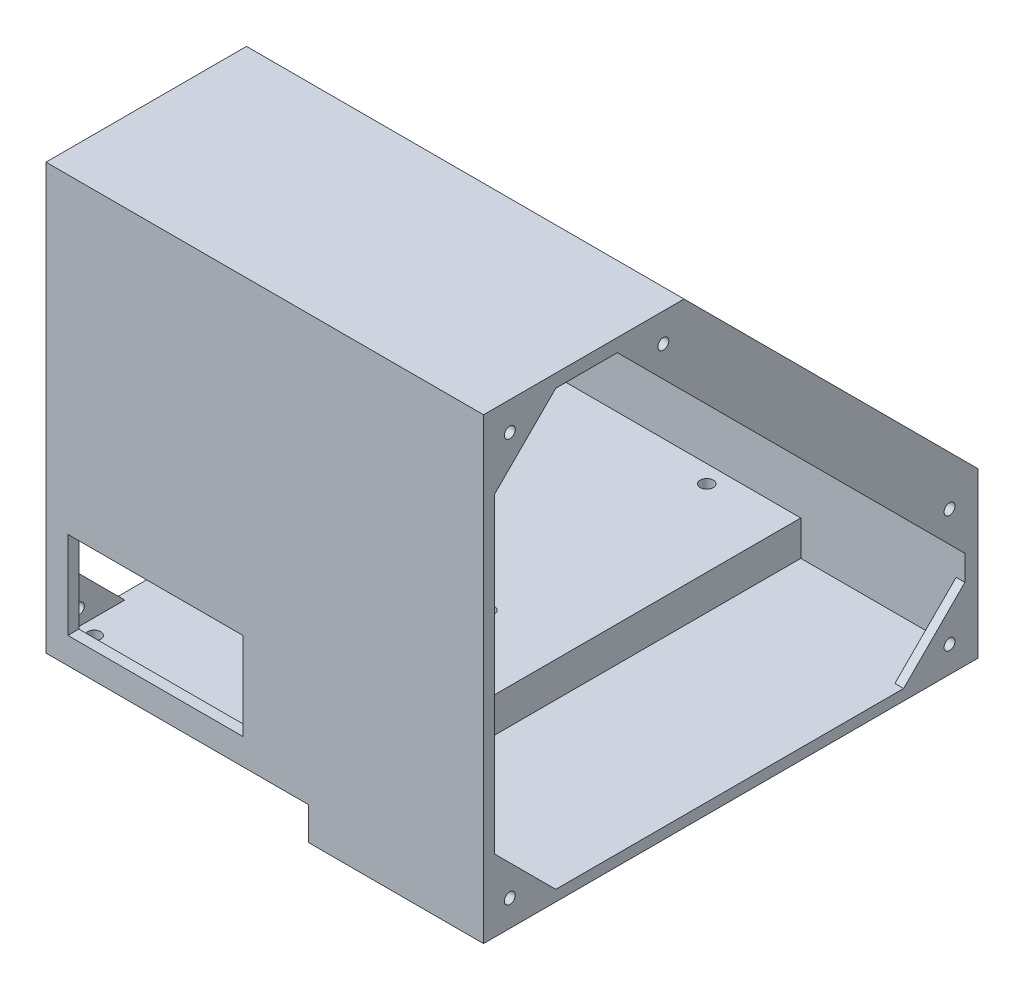
SolidWorks part; units mm, degrees
ref_plane "Front Plane" through (0, 0, 0) normal (0, 0, 1) x (1, 0, 0)
ref_plane "Top Plane" through (0, 0, 0) normal (0, 1, 0) x (1, 0, 0)
ref_plane "Right Plane" through (0, 0, 0) normal (1, 0, 0) x (0, 0, -1)
sketch "Sketch1" plane through (0, 0, 0) normal (1, 0, 0) x (0, 0, -1)
  line L0 (0, 0) -> (0, 30)
  line L1 (0, 30) -> (-67.1751, 97.1751)
  line L2 (-67.1751, 97.1751) -> (-113, 97.1751)
  line L3 (-113, 97.1751) -> (-113, 94.1751)
  line L4 (-113, 94.1751) -> (-68.4178, 94.1751)
  line L5 (-68.4178, 94.1751) -> (-3, 28.7574)
  line L6 (-3, 28.7574) -> (-3, 0)
  line L7 (-3, 0) -> (0, 0)
  line L8 (-3, 28.7574) -> (0, 28.7574) construction
  line L9 (-3, 28.7574) -> (-0.8787, 30.8787) construction
  line L10 (-68.4178, 94.1751) -> (-68.4178, 97.1751) construction
  dimension "D1" = 95
  dimension "D2" = 135
  dimension "D3" = 3
  dimension "D4" = 30
  dimension "D5" = 110
extrude "Boss-Extrude1" add sketch "Sketch1" along normal blind 100
sketch "Sketch2" plane through (0, 0, 0) normal (0, -1, 0) x (1, 0, 0)
  line L0 (100, 0) -> (0, 0) construction
  line L1 (100, 3) -> (60, 3)
  line L2 (100, 3) -> (100, 0)
  line L3 (100, 0) -> (60, 0)
  line L4 (60, 3) -> (60, 0)
  dimension "D1" = 40
extrude "Boss-Extrude2" add sketch "Sketch2" along normal blind 7.5
sketch "Sketch3" plane through (0, 0, 0) normal (0, -1, 0) x (1, 0, 0)
  line L0 (0, 3) -> (0, 113)
  line L1 (0, 113) -> (60, 113)
  line L2 (60, 113) -> (60, 3)
  line L3 (60, 3) -> (0, 3)
  line L4 (100, 3) -> (0, 3) construction
  line L5 (60, 3) -> (0, 3) construction
  dimension "D1" = 110
extrude "Boss-Extrude3" add sketch "Sketch3" against normal blind 3
sketch "Sketch4" plane through (0, 0, 3) normal (0, 0, 1) x (1, 0, 0)
  line L0 (60, 3) -> (60, -7.5)
  line L1 (60, -7.5) -> (100, -7.5)
  line L2 (100, -7.5) -> (100, -5)
  line L3 (100, 28.7574) -> (100, -7.5) construction
  line L4 (100, -5) -> (62.5, -5)
  line L5 (62.5, -5) -> (62.5, 3)
  line L6 (62.5, 3) -> (60, 3)
  dimension "D1" = 2.5
extrude "Boss-Extrude4" add sketch "Sketch4" along normal up to surface (110 mm away) up to face at (30, 1.5, 113)
sketch "Sketch5" plane through (0, 94.1751, 0) normal (0, -1, 0) x (1, 0, 0)
  line L0 (100, 113) -> (100, 68.4178) construction
  line L1 (0, 113) -> (100, 113)
  line L2 (0, 113) -> (0, 110.5)
  line L3 (0, 110.5) -> (100, 110.5)
  line L4 (100, 113) -> (100, 110.5)
  dimension "D1" = 2.5
extrude "Boss-Extrude5" add sketch "Sketch5" along normal up to next
sketch "Sketch6" plane through (0, 0, 0) normal (0, -1, 0) x (1, 0, 0)
  circle A0 centre (5, 107) radius 1.5 construction
  circle A1 centre (45, 107) radius 1.5 construction
  circle A2 centre (45, 57) radius 1.5 construction
  circle A3 centre (5, 57) radius 1.5 construction
  circle A4 centre (5, 7) radius 1.5 construction
  circle A5 centre (45, 7) radius 1.5 construction
  circle A6 centre (5, 107) radius 1.5
  circle A7 centre (45, 107) radius 1.5
  circle A8 centre (45, 57) radius 1.5
  circle A9 centre (5, 57) radius 1.5
  circle A10 centre (5, 7) radius 1.5
  circle A11 centre (45, 7) radius 1.5
extrude "Cut-Extrude1" cut sketch "Sketch6" against normal up to next
sketch "Sketch7" plane through (100, 0, 0) normal (1, 0, 0) x (0, 0, -1)
  line L0 (-110.5, -5) -> (-110.5, 9)
  line L1 (-110.5, -5) -> (-110.5, 94.1751) construction
  line L2 (-110.5, 9) -> (-96.5, -5)
  line L3 (-110.5, -5) -> (-3, -5) construction
  line L4 (-96.5, -5) -> (-110.5, -5)
  line L5 (-110.5, 94.1751) -> (-110.5, 80.1751)
  line L6 (-110.5, 80.1751) -> (-96.5, 94.1751)
  line L7 (-110.5, 94.1751) -> (-68.4178, 94.1751) construction
  line L8 (-96.5, 94.1751) -> (-110.5, 94.1751)
  line L9 (-82.4178, 94.1751) -> (-3, 14.7574)
  line L10 (-3, 28.7574) -> (-3, -5) construction
  line L11 (-3, 14.7574) -> (-3, 28.7574)
  line L12 (-3, 28.7574) -> (-68.4178, 94.1751)
  line L13 (-68.4178, 94.1751) -> (-82.4178, 94.1751)
  line L14 (-17, -5) -> (-3, 9)
  line L15 (-3, 9) -> (-3, -5)
  line L16 (-3, -5) -> (-17, -5)
  line L17 (-110.5, -5) -> (-103.5, 2) construction
  line L18 (-3, -5) -> (-10, 2) construction
  line L19 (-3, 28.7574) -> (-10, 21.7574) construction
  line L20 (-68.4178, 94.1751) -> (-75.4178, 87.1751) construction
  line L21 (-110.5, 94.1751) -> (-103.5, 87.1751) construction
  circle A0 centre (-107, -1.5) radius 1.25
  circle A1 centre (-6.5, -1.5) radius 1 construction
  circle A2 centre (-6.5, -1.5) radius 1.25
  circle A3 centre (-6.5, 25.2574) radius 1.25
  circle A4 centre (-71.9178, 90.6751) radius 1.25
  circle A5 centre (-107, 90.6751) radius 1.25
  dimension "D2" = 2
  dimension "D1" = 14
  dimension "D3" = 0.25
extrude "Boss-Extrude6" add sketch "Sketch7" against normal blind 2
sketch "Sketch8" plane through (0, 15, -15) normal (0, 0.7071, -0.7071) x (1, 0, 0)
  line L0 (96.675, -112.2132) -> (100, -112.2132) construction
  line L1 (96.675, -25.2132) -> (3.325, -25.2132) construction
  line L2 (96.675, -25.2132) -> (96.675, -112.2132) construction
  line L3 (96.675, -112.2132) -> (3.325, -112.2132) construction
  line L4 (3.325, -25.2132) -> (3.325, -112.2132) construction
  line L5 (100, -21.2132) -> (100, -116.2132) construction
  line L6 (96.675, -112.2132) -> (96.675, -116.2132) construction
  line L7 (100, -116.2132) -> (0, -116.2132) construction
  line L8 (3.325, -21.2132) -> (3.325, -25.2132) construction
  line L9 (100, -21.2132) -> (0, -21.2132) construction
  line L10 (3.325, -25.2132) -> (0, -25.2132) construction
  line L11 (0, -21.2132) -> (0, -116.2132) construction
  line L12 (96.675, -109.4882) -> (93.95, -109.4882) construction
  line L13 (93.95, -109.4882) -> (93.95, -112.2132) construction
  line L14 (93.95, -109.4882) -> (6.05, -109.4882) construction
  line L15 (6.05, -109.4882) -> (3.325, -109.4882) construction
  line L16 (93.95, -109.4882) -> (93.95, -44.5882) construction
  line L17 (93.95, -44.5882) -> (6.05, -44.5882) construction
  line L18 (6.05, -44.5882) -> (6.05, -109.4882) construction
  line L19 (89.025, -102.7132) -> (96.675, -102.7132) construction
  line L20 (89.025, -102.7132) -> (11.025, -102.7132)
  line L21 (89.025, -102.7132) -> (89.025, -58.8437)
  line L22 (89.025, -58.8437) -> (11.025, -58.8437)
  line L23 (11.025, -102.7132) -> (11.025, -58.8437)
  line L24 (89.025, -102.7132) -> (89.025, -112.2132) construction
  line L25 (51.495, -25.2132) -> (51.495, -33.7132) construction
  line L26 (51.495, -33.7132) -> (96.675, -33.7132) construction
  line L28 (33.175, -28.2132) -> (6.175, -28.2132)
  line L29 (33.175, -28.2132) -> (33.175, -40.2132)
  line L30 (33.175, -40.2132) -> (6.175, -40.2132)
  line L31 (6.175, -28.2132) -> (6.175, -40.2132)
  circle A0 centre (6.05, -109.4882) radius 1.5 construction
  circle A1 centre (6.05, -109.4882) radius 1.75
  circle A2 centre (93.95, -109.4882) radius 1.75
  circle A3 centre (93.95, -44.5882) radius 1.75
  circle A4 centre (6.05, -44.5882) radius 1.75
  circle A5 centre (51.495, -33.7132) radius 2.5
  dimension "D5" = 3
  dimension "D13" = 5
  dimension "D1" = 87
  dimension "D2" = 93.35
  dimension "D3" = 87.9
  dimension "D6" = 64.9
  dimension "D7" = 7.65
  dimension "D8" = 9.5
  dimension "D9" = 53.3695
  dimension "D10" = 85.65
  dimension "D11" = 8.5
  dimension "D12" = 45.18
  dimension "D14" = 63.5
  dimension "D15" = 90.5
  dimension "D16" = 27
  dimension "D17" = 3
  dimension "D18" = 12
  dimension "D4" = 0.25
extrude "Cut-Extrude2" cut sketch "Sketch8" against normal up to next
sketch "Sketch9" plane through (0, 12.8787, -12.8787) normal (0, -0.7071, 0.7071) x (1, 0, 0)
  line L0 (89.025, 58.8437) -> (89.025, 49.7132) construction
  line L1 (5.025, 49.7132) -> (92.025, 49.7132)
  line L2 (5.025, 49.7132) -> (5.025, 105.7132)
  line L3 (5.025, 105.7132) -> (92.025, 105.7132)
  line L4 (92.025, 49.7132) -> (92.025, 105.7132)
  line L5 (89.025, 58.8437) -> (92.025, 58.8437) construction
  line L6 (11.025, 102.7132) -> (11.025, 105.7132) construction
  line L7 (11.025, 102.7132) -> (5.025, 102.7132) construction
  line L8 (11.025, 102.7132) -> (89.025, 102.7132) construction
  line L9 (6.175, 28.2132) -> (33.175, 28.2132) construction
  line L10 (33.175, 28.2132) -> (33.175, 40.2132) construction
  line L11 (33.175, 40.2132) -> (6.175, 40.2132) construction
  line L12 (6.175, 40.2132) -> (6.175, 28.2132) construction
  line L13 (6.175, 28.2132) -> (33.175, 28.2132) construction
  line L14 (33.175, 28.2132) -> (33.175, 40.2132) construction
  line L15 (33.175, 40.2132) -> (6.175, 40.2132) construction
  line L16 (6.175, 40.2132) -> (6.175, 28.2132) construction
  line L17 (4.675, 26.7132) -> (34.675, 26.7132)
  line L18 (34.675, 26.7132) -> (34.675, 41.7132)
  line L19 (34.675, 41.7132) -> (4.675, 41.7132)
  line L20 (4.675, 41.7132) -> (4.675, 26.7132)
  dimension "D1" = 87
  dimension "D2" = 56
  dimension "D3" = 3
  dimension "D4" = 3
  dimension "D5" = 1.5
extrude "Cut-Extrude3" cut sketch "Sketch9" against normal offset from surface (2 mm away) 1 up to face at (93.95, 93.6573, 63.6573)
sketch "Sketch10" plane through (0, 0, 110.5) normal (0, 0, -1) x (-1, 0, 0)
  line L0 (-5, 3) -> (-5, 6) construction
  line L1 (-5, 6) -> (-45, 6)
  line L2 (-5, 6) -> (-5, 26)
  line L3 (-5, 26) -> (-45, 26)
  line L4 (-45, 6) -> (-45, 26)
  line L5 (-62.5, 3) -> (0, 3) construction
  line L6 (-5, 6) -> (0, 6) construction
  line L7 (0, 3) -> (0, 94.1751) construction
  dimension "D1" = 3
  dimension "D2" = 5
  dimension "D3" = 40
  dimension "D4" = 20
extrude "Cut-Extrude4" cut sketch "Sketch10" against normal through all
sketch "Sketch11" plane through (0, 0, 0) normal (-1, 0, 0) x (0, 0, 1)
  line L0 (110.5, 94.1751) -> (110.5, 80.1751) construction
  line L1 (110.5, 80.1751) -> (96.5, 94.1751) construction
  line L2 (96.5, 94.1751) -> (110.5, 94.1751) construction
  line L3 (68.4178, 94.1751) -> (82.4178, 94.1751) construction
  line L4 (3, 28.7574) -> (68.4178, 94.1751) construction
  line L5 (82.4178, 94.1751) -> (3, 14.7574) construction
  line L6 (3, 14.7574) -> (3, 28.7574) construction
  line L7 (110.5, 94.1751) -> (110.5, 80.1751)
  line L8 (110.5, 80.1751) -> (96.5, 94.1751)
  line L9 (96.5, 94.1751) -> (110.5, 94.1751)
  line L10 (68.4178, 94.1751) -> (82.4178, 94.1751)
  line L11 (3, 28.7574) -> (68.4178, 94.1751)
  line L12 (82.4178, 94.1751) -> (4.1213, 15.8787)
  line L13 (3, 14.7574) -> (3, 28.7574)
  line L17 (110.5, 3) -> (3, 3) construction
  line L18 (17, 3) -> (3, 3)
  line L19 (96.5, 3) -> (110.5, 17)
  line L20 (110.5, 3) -> (110.5, 94.1751) construction
  line L21 (110.5, 17) -> (110.5, 3)
  line L22 (110.5, 3) -> (96.5, 3)
  line L23 (4.1213, 15.8787) -> (3, 14.7574) construction
  line L24 (4.1213, 15.8787) -> (17, 3)
  line L25 (3, 14.7574) -> (3, 3)
  line L26 (3, 3) -> (10, 10) construction
  line L27 (110.5, 3) -> (103.5, 10) construction
  circle A0 centre (71.9178, 90.6751) radius 1.25 construction
  circle A1 centre (107, 90.6751) radius 1.25 construction
  circle A2 centre (6.5, 25.2574) radius 1.25 construction
  circle A3 centre (71.9178, 90.6751) radius 1.25
  circle A4 centre (107, 90.6751) radius 1.25
  circle A5 centre (6.5, 25.2574) radius 1.25
  circle A6 centre (107, 6.5) radius 1.25
  circle A7 centre (6.5, 6.5) radius 1.25
extrude "Boss-Extrude7" add sketch "Sketch11" against normal blind 1.5
sketch "Sketch12" plane through (0, 0, 0) normal (-1, 0, 0) x (0, 0, 1)
  line L0 (21.2132, 49.0919) -> (55.1543, 83.033)
  line L1 (21.2132, 49.0919) -> (26.163, 44.1421)
  line L2 (55.1543, 83.033) -> (60.1041, 78.0833)
  line L3 (26.163, 44.1421) -> (60.1041, 78.0833)
  line L4 (22.2739, 48.0312) -> (61.8718, 87.6292) construction
  dimension "D1" = 1.5
  dimension "D2" = 7
  dimension "D3" = 48
extrude "Cut-Extrude5" cut sketch "Sketch12" against normal up to next
equation "\"Tolerance\" = 0.25mm"
equation "\"Pocket_Head_M5\"= 8mm"
equation "\"Pocket_Head_M4\" = 7mm"
equation "\"Pocket_Nut_M4\" = 7mm"
equation "\"Pocket_Nut_M2.5\" = 5mm"
equation "\"Pocket_Nut_M5\"= 8mm"
equation "\"Pocket_Nut_M3\"= 5.5mm"
equation "\"Pocket_Head_M3\"= 5.5mm"
equation "\"Pocket_Head_M2.5\" = 4.7mm"
equation "\"Pocket_Head_M6\" = 10mm"
equation "\"D3@Sketch7\"=\"Tolerance\""
equation "\"D4@Sketch8\"=\"Tolerance\""
